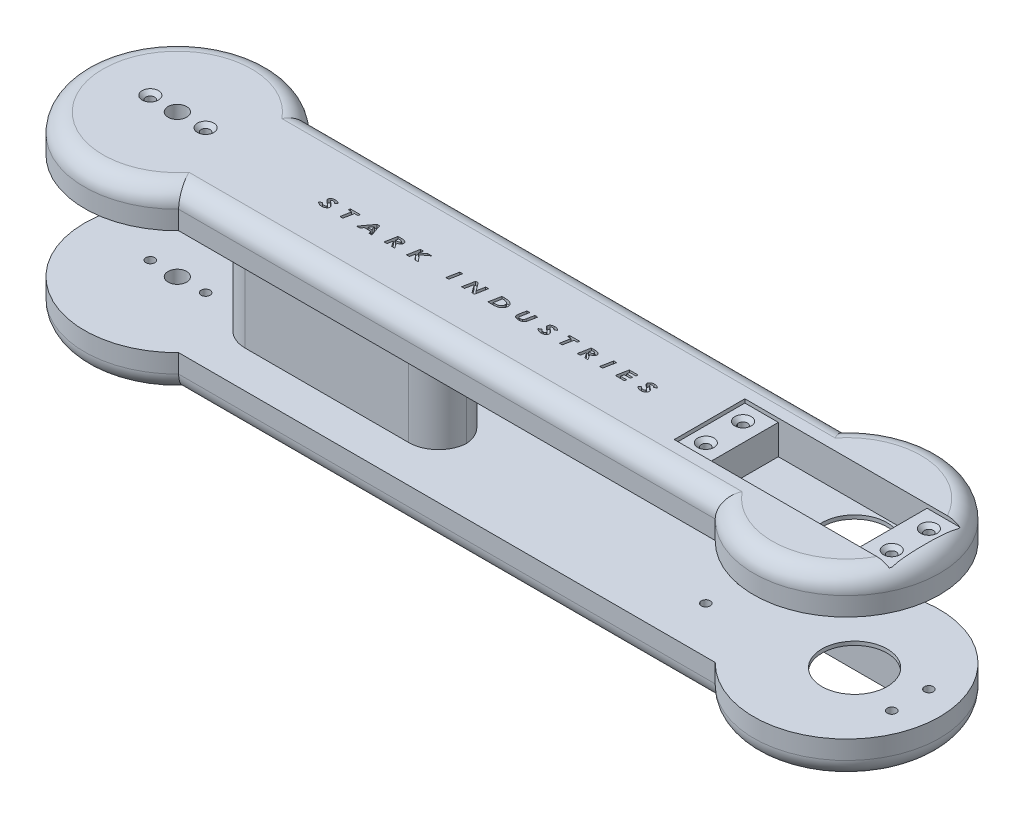
SolidWorks part; units mm, degrees
ref_plane "Front Plane" through (0, 0, 0) normal (0, 0, 1) x (1, 0, 0)
ref_plane "Top Plane" through (0, 0, 0) normal (0, 1, 0) x (1, 0, 0)
ref_plane "Right Plane" through (0, 0, 0) normal (1, 0, 0) x (0, 0, -1)
sketch "Sketch1" plane through (0, 0, 0) normal (0, 1, 0) x (1, 0, 0)
  line L0 (-90, 23.3289) -> (-90, -48.0567) construction
  line L1 (0, 0) -> (-180, 0)
  line L2 (0, 0) -> (0, -35)
  line L3 (0, -35) -> (-180, -35)
  line L4 (-180, 0) -> (-180, -35)
  circle A0 centre (-180, -17.5) radius 25
  circle A1 centre (0, -17.5) radius 25
  dimension "D3" = 50
  dimension "D4" = 50
  dimension "D1" = 180
  dimension "D2" = 35
extrude "Boss-Extrude1" add sketch "Sketch1" along normal blind 20 contours L0 L1 A0 L3 | L1 L0 L3 A1 region at (-56.3546, 0, 17.5) region at (-123.6454, 0, 17.5)
extrude "Boss-Extrude2" add sketch "Sketch1<3>" along normal blind 10 contours L1 A0 L3 L4 | L3 A1 L1 L2 | L1 A1 L3 L2 | L3 A0 L1 L4 region at (-11.481, 0, 17.5) region at (7.8453, 0, 17.5) region at (-168.519, 0, 17.5) region at (-187.8453, 0, 17.5)
sketch "Sketch1<3>" plane through (0, 0, 0) normal (0, 1, 0) x (1, 0, 0) same geometry as "Sketch1"
sketch "Sketch4" plane through (0, 10, 0) normal (0, 1, 0) x (1, 0, 0)
  circle A0 centre (-180, -17.5) radius 2.5
  dimension "D1" = 5
extrude "Cut-Extrude1" cut sketch "Sketch4" against normal through all
hole_wizard "CSK for M2 Flat Head Machine Screw2" positions "Sketch5" profile "Sketch6" countersink size "M2" standard "ANSI Metric" end condition through all
sketch "Sketch5" plane through (0, 10, 0) normal (0, 1, 0) x (1, 0, 0)
  circle A0 centre (-180, -17.5) radius 2.5 construction
  point P0 (-172.5006, -17.4081)
  point P2 (-187.5, -17.2782)
  dimension "D1" = 15
  dimension "D2" = 7.5
  dimension "D3" = 7.5
sketch "Sketch6" plane through (-172.5006, 10, 17.4081) normal (1, 0, 0) x (0, 0, 1)
  line L0 (0, 0) -> (0, 10)
  line L1 (0, 10) -> (1.2, 10)
  line L2 (1.2, 10) -> (1.2, 1)
  line L3 (1.2, 1) -> (2.2, 0)
  line L5 (2.2, 0) -> (0, 0)
  line L6 (-1.2, 1) -> (-2.2, 0) construction
  line L11 (0, -6.35) -> (0, 107.95) construction
  dimension "Thru Hole Dia." = 2.4
  dimension "Thru Hole Depth" = 10
  dimension "Near C'Sink Dia." = 4.4
  dimension "Near C'Sink Angle" = 90
sketch "Sketch7" plane through (0, 20, 0) normal (0, 1, 0) x (1, 0, 0)
  line L1 (-164.876, 0) -> (-149.2821, 0)
  line L2 (-164.876, 0) -> (-164.876, -35)
  line L3 (-164.876, -35) -> (-149.2821, -35)
  line L4 (-149.2821, 0) -> (-149.2821, -35)
  line L6 (-27.8721, 0) -> (-12.9465, 0)
  line L7 (-27.8721, 0) -> (-27.8721, -35)
  line L8 (-27.8721, -35) -> (-12.9465, -35)
  line L9 (-12.9465, 0) -> (-12.9465, -35)
extrude "Cut-Extrude2" cut sketch "Sketch7" against normal up to surface (10 mm away)
sketch "Sketch8" plane through (0, 0, 0) normal (0, 1, 0) x (1, 0, 0)
  line L0 (-27.8721, -17.5) -> (-27.8721, -8)
  line L1 (-27.8721, 0) -> (-27.8721, -35) construction
  line L2 (-27.8721, -17.5) -> (-27.8721, -27)
  line L3 (-27.8721, -27) -> (12.1279, -27)
  line L4 (12.1279, -27) -> (12.1279, -8)
  line L5 (-27.8721, -8) -> (12.1279, -8)
  line L7 (-27.8721, -27) -> (-36.8721, -27)
  line L8 (-27.8721, -27) -> (-27.8721, -8)
  line L9 (-27.8721, -8) -> (-36.8721, -8)
  line L10 (-36.8721, -27) -> (-36.8721, -8)
  line L11 (12.1279, -27) -> (21.1279, -27)
  line L12 (12.1279, -27) -> (12.1279, -8)
  line L13 (12.1279, -8) -> (21.1279, -8)
  line L14 (21.1279, -27) -> (21.1279, -8)
  dimension "D1" = 9.5
  dimension "D2" = 9.5
  dimension "D3" = 40
  dimension "D4" = 9
  dimension "D5" = 9
extrude "Cut-Extrude3" cut sketch "Sketch8" along normal blind 10 from offset 1 contours L5 L0 L2 L3 L4 region at (-7.8721, 0, 17.5)
extrude "Cut-Extrude4" cut sketch "Sketch8<4>" against normal blind 11 from surface contours L11 L14 L13 L4 | L10 L7 L2 L0 L9 region at (-32.3721, 0, 17.5) region at (16.6279, 0, 17.5) starting at face at (-88.5771, 20, 17.5)
sketch "Sketch8<4>" plane through (0, 0, 0) normal (0, 1, 0) x (1, 0, 0) same geometry as "Sketch8"
hole_wizard "CSK for M2 Flat Head Machine Screw3" positions "Sketch12" profile "Sketch13" countersink size "M2" standard "ANSI Metric" end condition through all
sketch "Sketch12" plane through (0, 9, 0) normal (0, 1, 0) x (1, 0, 0)
  line L0 (-36.8721, -8) -> (-27.8721, -8) construction
  line L1 (-36.8721, -27) -> (-27.8721, -27) construction
  point P0 (-32.8721, -12.5)
  point P2 (-32.8721, -22.5)
  dimension "D2" = 4.5
  dimension "D3" = 4.5
sketch "Sketch13" plane through (-32.8721, 9, 12.5) normal (1, 0, 0) x (0, 0, 1)
  line L0 (0, 0) -> (0, 9)
  line L1 (0, 9) -> (1.2, 9)
  line L2 (1.2, 9) -> (1.2, 1)
  line L3 (1.2, 1) -> (2.2, 0)
  line L5 (2.2, 0) -> (0, 0)
  line L6 (-1.2, 1) -> (-2.2, 0) construction
  line L11 (0, -6.35) -> (0, 107.95) construction
  dimension "Thru Hole Dia." = 2.4
  dimension "Thru Hole Depth" = 9
  dimension "Near C'Sink Dia." = 4.4
  dimension "Near C'Sink Angle" = 90
hole_wizard "CSK for M2 Flat Head Machine Screw4" positions "Sketch14" profile "Sketch15" countersink size "M2" standard "ANSI Metric" end condition through all
sketch "Sketch14" plane through (0, 9, 0) normal (0, 1, 0) x (1, 0, 0)
  line L0 (21.1279, -8) -> (12.1279, -8) construction
  line L1 (21.1279, -27) -> (12.1279, -27) construction
  point P0 (17.1279, -12.5)
  point P2 (17.1279, -22.5)
  dimension "D2" = 4.5
  dimension "D3" = 4.5
sketch "Sketch15" plane through (17.1279, 9, 12.5) normal (1, 0, 0) x (0, 0, 1)
  line L0 (0, 0) -> (0, 9)
  line L1 (0, 9) -> (1.2, 9)
  line L2 (1.2, 9) -> (1.2, 1)
  line L3 (1.2, 1) -> (2.2, 0)
  line L5 (2.2, 0) -> (0, 0)
  line L6 (-1.2, 1) -> (-2.2, 0) construction
  line L11 (0, -6.35) -> (0, 107.95) construction
  dimension "Thru Hole Dia." = 2.4
  dimension "Thru Hole Depth" = 9
  dimension "Near C'Sink Dia." = 4.4
  dimension "Near C'Sink Angle" = 90
sketch "Sketch16" plane through (0, 1, 0) normal (0, 1, 0) x (1, 0, 0)
  line L0 (12.1279, -8) -> (12.1279, -27) construction
  circle A0 centre (2.1279, -17.5) radius 8.7784
  dimension "D1" = 10
extrude "Cut-Extrude5" cut sketch "Sketch16" against normal blind 16 contours A0
sketch "Sketch17" plane through (0, 0, 0) normal (0, 0, 1) x (1, 0, 0)
  line L0 (-17.8536, 10) -> (-27.8721, 10) construction
  line L1 (-150.6263, 20.571) -> (-26.5586, 20.571)
  line L2 (-150.6263, 20.571) -> (-150.6263, 10)
  line L3 (-150.6263, 10) -> (-26.5586, 10)
  line L4 (-26.5586, 20.571) -> (-26.5586, 10)
extrude "Cut-Extrude6" cut sketch "Sketch17" along normal up to surface (35 mm away) up to face at (-89.2885, 10, 35)
sketch "Sketch20" plane through (0, 10, 0) normal (0, 1, 0) x (1, 0, 0)
  line L0 (-162.1464, 0) -> (-17.8536, 0) construction
  circle A0 centre (-180, -17.5) radius 2.5 construction
  text T0 "<b><i>STARK INDUSTRIES</i></b>" font "Century Gothic" height 3.175
  point P3 (0, 0)
  dimension "D1" = 40
  dimension "D2" = 20
extrude "Cut-Extrude7" cut sketch "Sketch20" against normal blind 1
ref_plane "Plane2" through (0, -14.2, 0) normal (0, 1, 0) x (1, 0, 0)
fillet "Fillet7" radius 5 4 edges at (25, 10, 17.5) (-205, 10, 17.5) (-90, 10, 0) (-90, 10, 35)
mirror "Mirror1" about plane through (0, -14.2, 0) normal (0, 1, 0) of bodies 170
sketch "Sketch21" plane through (0, 0, 0) normal (0, -1, 0) x (1, 0, 0)
  line L1 (-162.2695, 25) -> (-102.2695, 25)
  line L2 (-162.2695, 25) -> (-162.2695, 10)
  line L3 (-162.2695, 10) -> (-102.2695, 10)
  line L4 (-102.2695, 25) -> (-102.2695, 10)
  dimension "D3" = 60
extrude "Boss-Extrude3" add sketch "Sketch21" along normal up to next
fillet "Fillet5" radius 8 4 edges at (-102.2695, -14.2, 25) (-102.2695, -14.2, 10) (-162.2695, -14.2, 10) (-162.2695, -14.2, 25)
